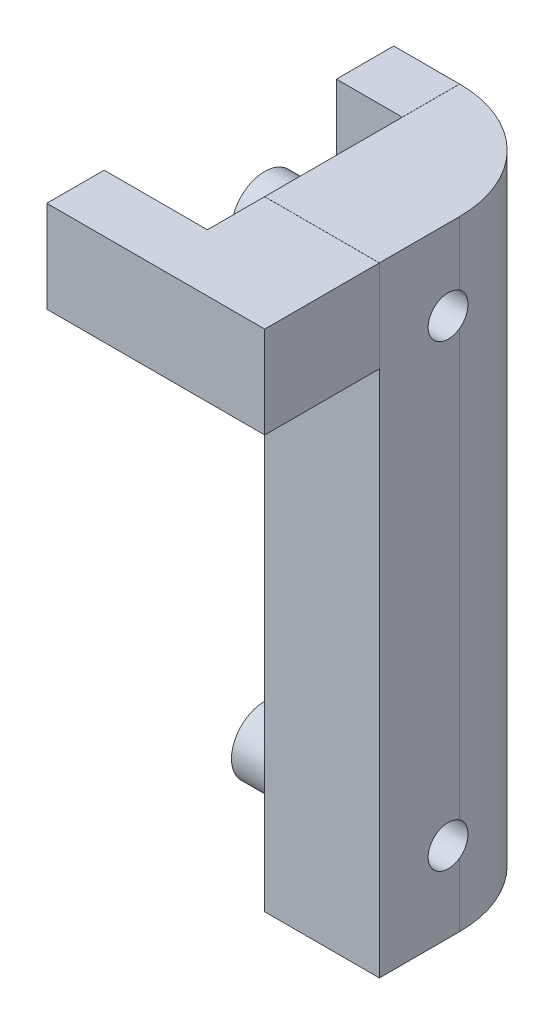
SolidWorks part; units mm, degrees
ref_plane "Front Plane" through (0, 0, 0) normal (0, 0, 1) x (1, 0, 0)
ref_plane "Top Plane" through (0, 0, 0) normal (0, 1, 0) x (1, 0, 0)
ref_plane "Right Plane" through (0, 0, 0) normal (1, 0, 0) x (0, 0, -1)
sketch "Sketch1" plane through (0, 0, 0) normal (1, 0, 0) x (0, 0, -1)
  line L1 (0, 0) -> (12, 0)
  line L2 (0, 0) -> (0, 54)
  line L3 (0, 54) -> (12, 54)
  line L4 (12, 0) -> (12, 54)
  dimension "D1" = 12
  dimension "D2" = 54
extrude "Boss-Extrude1" add sketch "Sketch1" along normal blind 10
sketch "Sketch2" plane through (0, 0, 0) normal (-1, 0, 0) x (0, 0, 1)
  line L0 (-12, 54) -> (0, 54) construction
  line L1 (0, 0) -> (-12, 0) construction
  line L3 (-12, 0) -> (-12, 54) construction
  circle A0 centre (-6, 47) radius 2.9
  circle A1 centre (-6, 7) radius 2.9
  dimension "D1" = 5.8
  dimension "D2" = 5.8
  dimension "D3" = 7
  dimension "D4" = 7
  dimension "D5" = 6
extrude "Boss-Extrude2" add sketch "Sketch2" along normal blind 18
sketch "Sketch3" plane through (-18, 0, 0) normal (-1, 0, 0) x (0, 0, 1)
  line L0 (-12, 0) -> (-12, 54) construction
  line L1 (-12, 0) -> (0, 0)
  line L2 (-12, 0) -> (-12, 54)
  line L3 (-12, 54) -> (0, 54)
  line L4 (0, 0) -> (0, 54)
  line L5 (-12, 54) -> (0, 54) construction
extrude "Boss-Extrude3" add sketch "Sketch3" along normal blind 10
sketch "Sketch4" plane through (10, 0, 0) normal (1, 0, 0) x (0, 0, -1)
  circle A0 centre (6, 47) radius 1.75
  circle A1 centre (6, 7) radius 1.75
  circle A2 centre (6, 47) radius 2.9 construction
  circle A3 centre (6, 7) radius 2.9 construction
  dimension "D1" = 3.5
  dimension "D2" = 3.5
extrude "Cut-Extrude1" cut sketch "Sketch4" against normal blind 50
sketch "Sketch5" plane through (0, 0, -12) normal (0, 0, -1) x (-1, 0, 0)
  line L1 (-10, 54) -> (28, 54)
  line L2 (-10, 54) -> (-10, 0)
  line L3 (-10, 0) -> (28, 0)
  line L4 (28, 54) -> (28, 0)
extrude "Boss-Extrude4" add sketch "Sketch5" along normal blind 5
fillet "Fillet1" radius 10 2 edges at (-28, 27, -17) (10, 27, -17)
sketch "Sketch6" plane through (0, 0, -12) normal (0, 0, 1) x (1, 0, 0)
  line L0 (0, 0) -> (-18, 0) construction
  line L1 (-6, 0) -> (-12, 0)
  line L2 (-6, 0) -> (-6, 54)
  line L3 (-6, 54) -> (-12, 54)
  line L4 (-12, 0) -> (-12, 54)
  line L5 (-18, 54) -> (0, 54) construction
  line L6 (-18, 54) -> (-18, 0) construction
  dimension "D1" = 6
  dimension "D2" = 6
extrude "Cut-Extrude2" cut sketch "Sketch6" along normal blind 15
sketch "Sketch7" plane through (0, 0, -12) normal (0, 0, 1) x (1, 0, 0)
  line L0 (0, 0) -> (-18, 0) construction
  line L1 (-18, 54) -> (-17.99, 54)
  line L2 (-18, 54) -> (-18, 0)
  line L3 (-18, 0) -> (-17.99, 0)
  line L4 (-17.99, 54) -> (-17.99, 0)
  line L5 (-18, 54) -> (0, 54) construction
  line L6 (0, 0) -> (-0.01, 0)
  line L7 (0, 0) -> (0, 54)
  line L8 (0, 54) -> (-0.01, 54)
  line L9 (-0.01, 0) -> (-0.01, 54)
  dimension "D1" = 0.01
  dimension "D2" = 0.01
extrude "Cut-Extrude3" cut sketch "Sketch7" against normal blind 12.5
sketch "Sketch8" plane through (0, 54, 0) normal (0, 1, 0) x (1, 0, 0)
  line L0 (-18, 0) -> (-18, -5)
  line L1 (-18, -5) -> (0, -5)
  line L2 (0, -5) -> (0, 0)
  line L3 (0, 0) -> (10, 0)
  line L4 (10, 0) -> (10, -10)
  line L5 (10, -10) -> (-28, -10)
  line L6 (-28, -10) -> (-28, 0)
  line L7 (-28, 0) -> (-18, 0)
  dimension "D1" = 5
  dimension "D2" = 10
extrude "Boss-Extrude5" add sketch "Sketch8" against normal blind 8
sketch "Sketch9" plane through (0, 46, 0) normal (0, -1, 0) x (1, 0, 0)
  line L0 (-28, 0) -> (-28, 10) construction
  line L1 (10, 0) -> (-28, 0)
  line L2 (10, 0) -> (10, 0.01)
  line L3 (10, 0.01) -> (-28, 0.01)
  line L4 (-28, 0) -> (-28, 0.01)
  dimension "D1" = 0.01
extrude "Cut-Extrude4" cut sketch "Sketch9" against normal blind 50
sketch "Sketch10" plane through (0, 0, -17) normal (0, 0, -1) x (-1, 0, 0)
  line L0 (17.99, 54) -> (0.01, 54) construction
  line L1 (7, 54) -> (18, 54)
  line L2 (7, 54) -> (7, 0)
  line L3 (7, 0) -> (18, 0)
  line L4 (18, 54) -> (18, 0)
  dimension "D1" = 11
extrude "Boss-Extrude6" add sketch "Sketch10" along normal blind 2.5
sketch "Sketch11" plane through (0, 54, 0) normal (0, 1, 0) x (1, 0, 0)
  line L0 (-18, 18.25) -> (-19.25, 19.5)
  line L1 (-18, 19.5) -> (-18, 17) construction
  line L2 (-19.25, 19.5) -> (-18, 19.5)
  line L3 (-18, 19.5) -> (-18, 18.25)
  line L4 (-7, 19.5) -> (-7, 18.25)
  line L5 (-7, 19.5) -> (-7, 17) construction
  line L6 (-7, 18.25) -> (-5.75, 19.5)
  line L7 (-5.75, 19.5) -> (-7, 19.5)
extrude "Boss-Extrude7" add sketch "Sketch11" against normal blind 54
sketch "Sketch13" plane through (0, 0, -17) normal (0, 0, -1) x (-1, 0, 0)
  line L0 (0.01, 54) -> (5.75, 54)
  line L1 (5.75, 54) -> (5.75, 39)
  line L2 (5.75, 54) -> (34.2997, 54)
  line L3 (4.75, 39) -> (5.75, 39)
  line L4 (0.01, 0) -> (0.01, 54) construction
  line L5 (0.01, 54) -> (0, 34)
  line L6 (0, 54) -> (0, 0) construction
  line L7 (0, 34) -> (2.4125, 42.9857)
  line L8 (2.4125, 42.9857) -> (4.4125, 42.9857)
  line L9 (4.4125, 42.9857) -> (4.75, 39)
  line L10 (4.75, 15) -> (5.75, 15)
  line L11 (34.2997, 54) -> (34.2997, -4.4763)
  line L12 (34.2997, -4.4763) -> (5.75, -4.4763)
  line L13 (5.75, -4.4763) -> (5.75, 0)
  line L14 (0, 20) -> (0, 34)
  line L15 (0, 20) -> (2.4125, 11.0143)
  line L16 (2.4125, 11.0143) -> (4.4125, 11.0143)
  line L17 (4.4125, 11.0143) -> (4.75, 15)
  line L18 (5.75, 15) -> (5.75, 0)
  line L19 (5.75, 0) -> (0.01, 0)
  line L20 (0.01, 0) -> (0, 20)
  line M14 (7, 0) -> (7, 54)
  line M15 (7, 54) -> (0.01, 54)
  line M16 (0.01, 54) -> (0.01, 0)
  line M17 (0.01, 0) -> (7, 0)
  dimension "D1" = 20
  dimension "D2" = 15
  dimension "D3" = 2
  dimension "D4" = 4
  dimension "D5" = 1
  dimension "D6" = 15
extrude "Cut-Extrude5" cut sketch "Sketch13" against normal up to surface (5 mm away) and the other way blind 10 contours L13 L12 L11 L2 M14 M17 | L10 L18 L1 L3 L9 L8 L7 L15 L16 L17 M17 M14 M15 M16 region at (-4.0568, 27, -17) region at (-20.6, 24.6675, -17) up to face at (-9, 27, -12)
sketch "Sketch15" plane through (0, 0, 10) normal (0, 0, 1) x (1, 0, 0)
  line L0 (-28, 54) -> (10, 54) construction
  line L1 (-9, 54) -> (-43.9841, 54)
  line L2 (-9, 54) -> (-9, -2.2739)
  line L3 (-9, -2.2739) -> (-43.9841, -2.2739)
  line L4 (-43.9841, 54) -> (-43.9841, -2.2739)
extrude "Cut-Extrude6" cut sketch "Sketch15" against normal through all both and the other way through all
sketch "Sketch16" plane through (-9, 0, 0) normal (-1, 0, 0) x (0, 0, 1)
  line L0 (5, 54) -> (10, 46) construction
  line L1 (10, 54) -> (5, 46) construction
  circle A0 centre (7.5, 50) radius 1
  dimension "D1" = 2
extrude "Boss-Extrude8" add sketch "Sketch16" along normal blind 1.5
